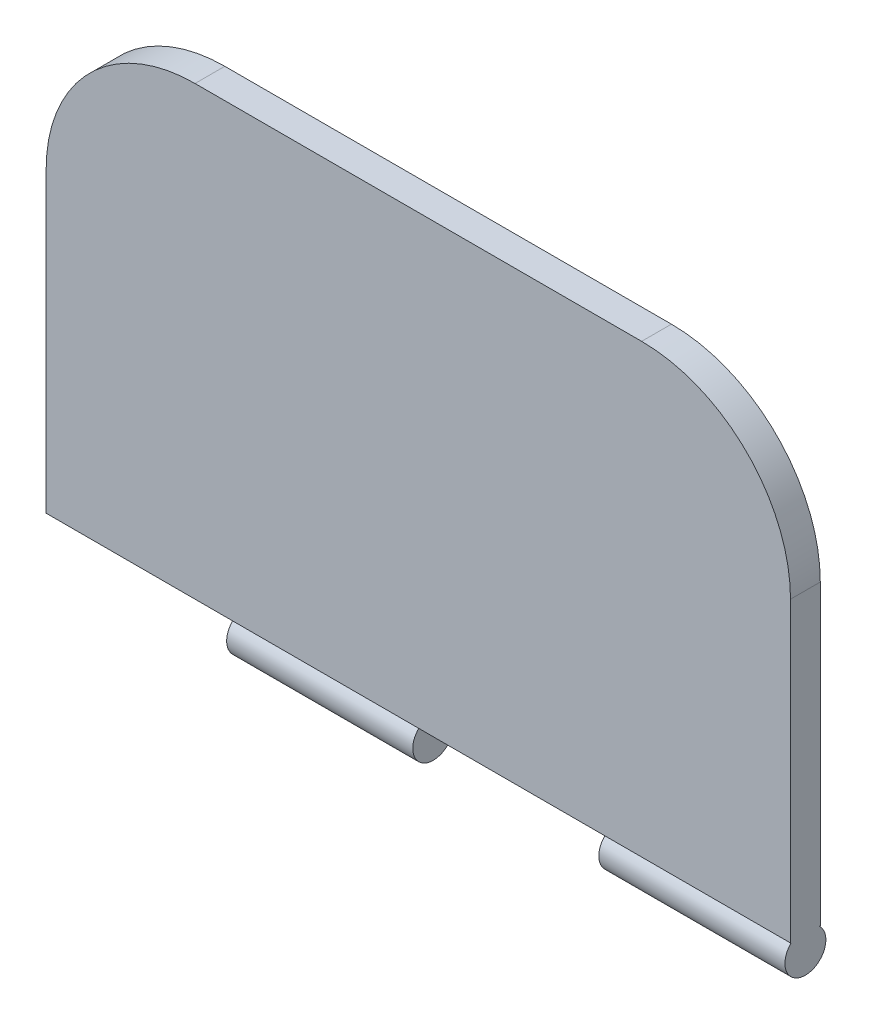
SolidWorks part; units mm, degrees
ref_plane "Front Plane" through (0, 0, 0) normal (0, 0, 1) x (1, 0, 0)
ref_plane "Top Plane" through (0, 0, 0) normal (0, 1, 0) x (1, 0, 0)
ref_plane "Right Plane" through (0, 0, 0) normal (1, 0, 0) x (0, 0, -1)
sketch "Sketch1" plane through (0, 0, 0) normal (0, 0, 1) x (1, 0, 0)
  line L1 (-15, 15) -> (15, 15)
  line L2 (-25, 5) -> (-25, -15)
  line L3 (-25, -15) -> (25, -15)
  line L4 (25, 5) -> (25, -15)
  line L5 (-25, 15) -> (25, -15) construction
  line L6 (-25, -15) -> (25, 15) construction
  arc A0 (25, 5) -> (15, 15) centre (15, 5) ccw
  arc A1 (-15, 15) -> (-25, 5) centre (-15, 5) ccw
  point P0 (0, 0)
  dimension "D3" = 10
  dimension "D1" = 50
  dimension "D2" = 30
extrude "Boss-Extrude1" add sketch "Sketch1" along normal blind 2
sketch "Sketch3" plane through (25, 0, 0) normal (1, 0, 0) x (0, 0, -1)
  line L2 (-2, -15) -> (0, -15) construction
  circle A0 centre (-1, -16) radius 1.375
  dimension "D1" = 2.75
  dimension "D2" = 1
extrude "Cut-Extrude1" cut sketch "Sketch3" against normal up to surface (50 mm away) up to face at (-25, -5, 1)
extrude "Boss-Extrude2" add sketch "Sketch3<2>" against normal blind 12.5
sketch "Sketch3<2>" plane through (25, 0, 0) normal (1, 0, 0) x (0, 0, -1) same geometry as "Sketch3"
ref_plane "Plane3" through (0, 0, 0) normal (-1, 0, 0) x (0, 0, 1)
sketch "Sketch5" plane through (0, 0, 0) normal (-1, 0, 0) x (0, 0, 1)
  circle A0 centre (1, -16) radius 1.375
extrude "Boss-Extrude3" add sketch "Sketch5" along normal blind 12.5
sketch "Sketch7" plane through (0, 0, 0) normal (0, 0, -1) x (-1, 0, 0)
  line L0 (0, 15) -> (0, -15) construction
  line L1 (-15, 15) -> (15, 15) construction
  line L2 (25, -15) -> (-25, -15) construction
  circle A0 centre (0, 0) radius 3.5
  dimension "D1" = 7
extrude "Cut-Extrude2" cut sketch "Sketch7" against normal blind 1
